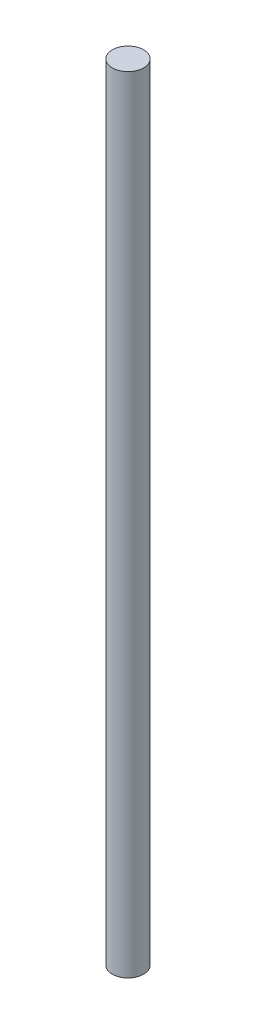
SolidWorks part; units mm, degrees
ref_plane "Front Plane" through (0, 0, 0) normal (0, 0, 1) x (1, 0, 0)
ref_plane "Top Plane" through (0, 0, 0) normal (0, 1, 0) x (1, 0, 0)
ref_plane "Right Plane" through (0, 0, 0) normal (1, 0, 0) x (0, 0, -1)
ref_axis "X" through (-88.99, 0, 0) along (1, 0, 0)
ref_axis "Y" through (0, 55, 0) along (0, -1, 0)
ref_axis "Z" through (0, 0, -88.99) along (0, 0, 1)
sketch "Sketch1" plane through (0, 0, 0) normal (0, 1, 0) x (1, 0, 0)
  circle A0 centre (0, 0) radius 1
  dimension "D1" = 2
extrude "Boss-Extrude1" add sketch "Sketch1" along normal blind 50
